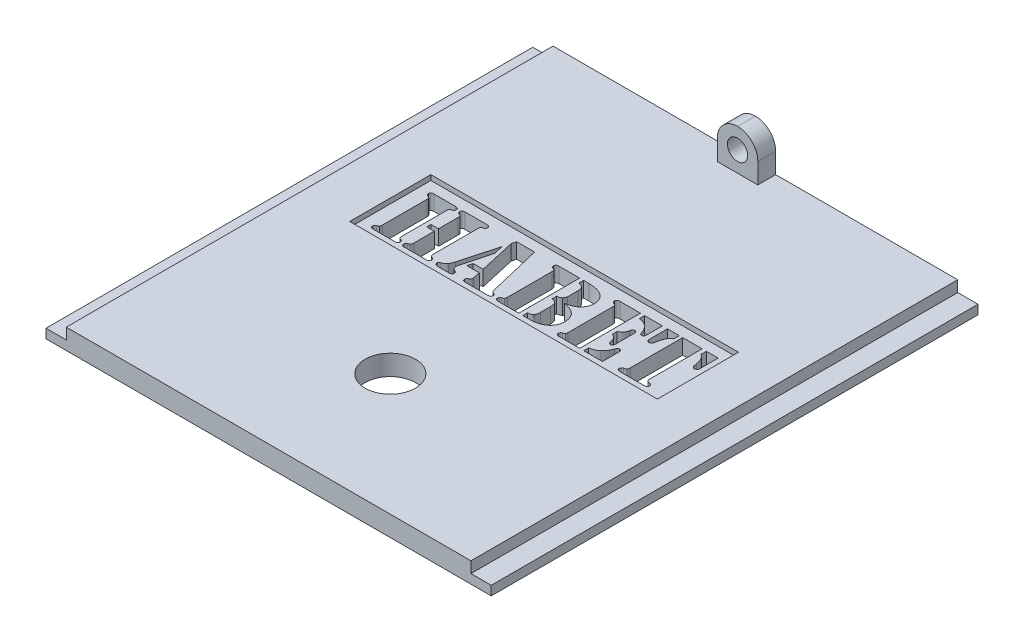
SolidWorks part; units mm, degrees
ref_plane "Front Plane" through (0, 0, 0) normal (0, 0, 1) x (1, 0, 0)
ref_plane "Top Plane" through (0, 0, 0) normal (0, 1, 0) x (1, 0, 0)
ref_plane "Right Plane" through (0, 0, 0) normal (1, 0, 0) x (0, 0, -1)
sketch "Sketch1" plane through (0, 0, 0) normal (0, 1, 0) x (1, 0, 0)
  line L1 (0, 0) -> (139.4003, 0)
  line L2 (0, 0) -> (0, 152.4)
  line L3 (0, 152.4) -> (139.4003, 152.4)
  line L4 (139.4003, 0) -> (139.4003, 152.4)
  dimension "D1" = 152.4
  dimension "D2" = 139.4003
extrude "Boss-Extrude1" add sketch "Sketch1" along normal blind 6.35
sketch "Sketch2" plane through (0, 6.35, 0) normal (0, 1, 0) x (1, 0, 0)
  line L0 (0, 0) -> (139.4003, 0) construction
  line L1 (0, 152.4) -> (6.35, 152.4)
  line L2 (0, 152.4) -> (0, 0)
  line L3 (0, 0) -> (6.35, 0)
  line L4 (6.35, 152.4) -> (6.35, 0)
  line L6 (139.4003, 152.4) -> (133.0503, 152.4)
  line L7 (139.4003, 152.4) -> (139.4003, 0)
  line L8 (139.4003, 0) -> (133.0503, 0)
  line L9 (133.0503, 152.4) -> (133.0503, 0)
  dimension "D1" = 6.35
  dimension "D2" = 6.35
extrude "Cut-Extrude1" cut sketch "Sketch2" against normal blind 3.4747
sketch "Sketch3" plane through (0, 6.35, 0) normal (0, 1, 0) x (1, 0, 0)
  line L0 (133.0503, 152.4) -> (6.35, 152.4) construction
  line L1 (63.3501, 152.4) -> (76.0501, 152.4)
  line L2 (63.3501, 152.4) -> (63.3501, 146.8137)
  line L3 (63.3501, 146.8137) -> (76.0501, 146.8137)
  line L4 (76.0501, 152.4) -> (76.0501, 146.8137)
  point P6 (69.7001, 152.4)
  point P7 (69.7001, 152.4)
  dimension "D1" = 12.7
extrude "Boss-Extrude2" add sketch "Sketch3" along normal blind 12.7
fillet "Fillet1" radius 6.35 2 edges at (63.3501, 19.05, -149.6068) (76.0501, 19.05, -149.6068)
sketch "Sketch4" plane through (0, 0, -152.4) normal (0, 0, -1) x (-1, 0, 0)
  circle A0 centre (-69.7001, 12.7) radius 3.175
  arc A1 (-63.3501, 12.7) -> (-69.7001, 19.05) centre (-69.7001, 12.7) ccw construction
  dimension "D1" = 3.175
extrude "Cut-Extrude2" cut sketch "Sketch4" against normal blind 6.35
sketch "Sketch7" plane through (0, 6.35, 0) normal (0, 1, 0) x (1, 0, 0)
  line L0 (6.35, 76.2) -> (133.0503, 76.2) construction
  line L3 (6.35, 0) -> (6.35, 152.4) construction
  line L4 (133.0503, 152.4) -> (133.0503, 0) construction
  text T0 "HABET" font "Stencil" height 19.05
extrude "Cut-Extrude7" cut sketch "Sketch7" against normal blind 6.35
sketch "Sketch9" plane through (0, 6.35, 0) normal (0, 1, 0) x (1, 0, 0)
  line L0 (35.9699, 95.25) -> (42.8243, 95.25) construction
  line L1 (22.0751, 98.425) -> (118.3835, 98.425)
  line L2 (22.0751, 98.425) -> (22.0751, 73.025)
  line L3 (22.0751, 73.025) -> (118.3835, 73.025)
  line L4 (118.3835, 98.425) -> (118.3835, 73.025)
  line L5 (42.8243, 76.2) -> (35.941, 76.2) construction
  line L6 (115.2085, 95.25) -> (115.2085, 89.5036) construction
  point P7 (39.3971, 95.25)
  point P10 (39.3826, 76.2)
  dimension "D1" = 3.175
  dimension "D2" = 3.175
  dimension "D3" = 3.175
  dimension "D4" = 3.175
extrude "Cut-Extrude8" cut sketch "Sketch9" against normal blind 1.5875
sketch "Sketch10" plane through (0, 6.35, 0) normal (0, 1, 0) x (1, 0, 0)
  line L0 (6.35, 0) -> (133.0503, 0) construction
  circle A0 centre (69.7001, 38.1) radius 7.874
  point P5 (69.7001, 0)
  dimension "D1" = 15.748
  dimension "D2" = 38.1
extrude "Cut-Extrude9" cut sketch "Sketch10" against normal through all
